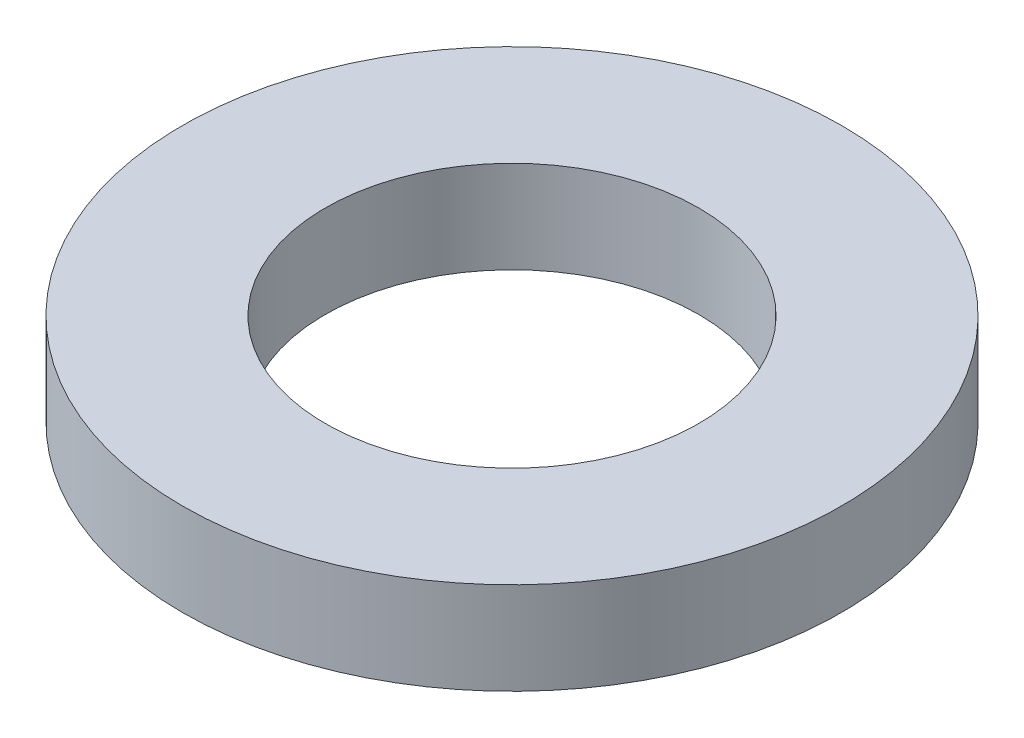
SolidWorks part; units mm, degrees
ref_plane "Front Plane" through (0, 0, 0) normal (0, 0, 1) x (1, 0, 0)
ref_plane "Top Plane" through (0, 0, 0) normal (0, 1, 0) x (1, 0, 0)
ref_plane "Right Plane" through (0, 0, 0) normal (1, 0, 0) x (0, 0, -1)
sketch "Sketch1" plane through (0, 0, 0) normal (0, 1, 0) x (1, 0, 0)
  circle A0 centre (0, 0) radius 75
  dimension "FLANGE_OD" = 150
extrude "Boss-Extrude1" add sketch "Sketch1" along normal blind 21
sketch "Sketch2" plane through (0, 0, 0) normal (0, 1, 0) x (1, 0, 0)
  circle A0 centre (0, 0) radius 42.5
  dimension "BORE_D" = 85
extrude "Cut-Extrude1" cut sketch "Sketch2" along normal through all
sketch "Sketch3" plane through (0, 21, 0) normal (0, 1, 0) x (1, 0, 0)
  circle A0 centre (0, 0) radius 27.0075 construction
  circle A1 centre (-27.0075, 0) radius 1.7894
  dimension "BOLT_D" = 3.5789
  dimension "BOLT_PCD" = 54.015
extrude "Cut-Extrude2" cut sketch "Sketch3" against normal blind 19.4408 rebuild error yes
pattern_circular "CirPattern1" count 3 over 360 rebuild error yes
